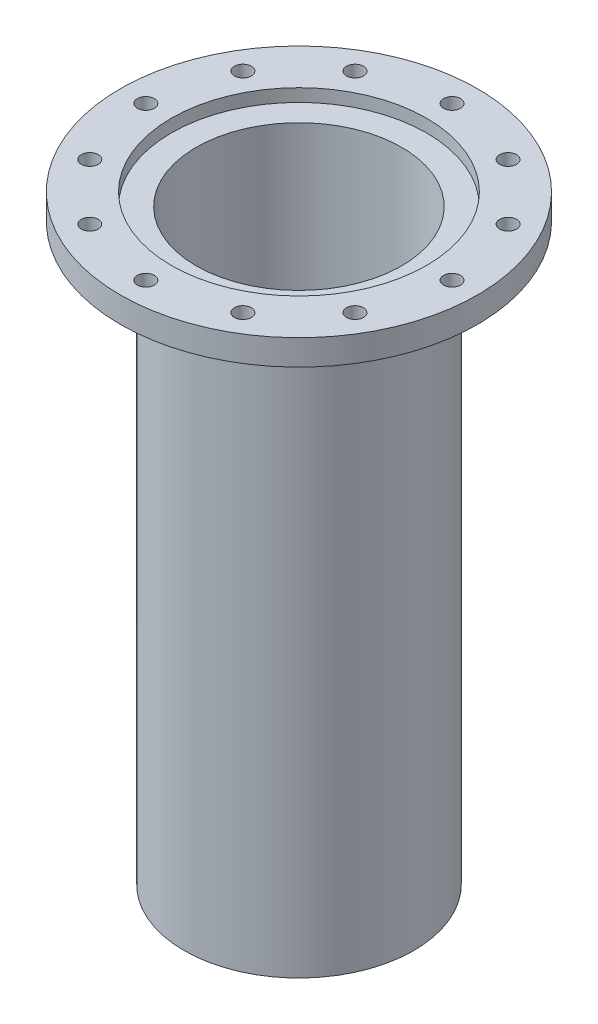
SolidWorks part; units mm, degrees
ref_plane "Front Plane" through (0, 0, 0) normal (0, 0, 1) x (1, 0, 0)
ref_plane "Top Plane" through (0, 0, 0) normal (0, 1, 0) x (1, 0, 0)
ref_plane "Right Plane" through (0, 0, 0) normal (1, 0, 0) x (0, 0, -1)
sketch "Sketch1" plane through (0, 0, 0) normal (0, 0, 1) x (1, 0, 0)
  line L0 (-63.5, 0) -> (-88.9, 0)
  line L1 (-88.9, 0) -> (-88.9, -12.7)
  line L2 (-88.9, -12.7) -> (-57.15, -12.7)
  line L3 (-57.15, -12.7) -> (-57.15, -298.45)
  line L4 (-57.15, -298.45) -> (-51.1302, -298.45)
  line L5 (-51.1302, -298.45) -> (-51.1302, -6.35)
  line L6 (-51.1302, -6.35) -> (-63.5, -6.35)
  line L7 (-63.5, -6.35) -> (-63.5, 0)
  line L8 (0, 0) -> (0, -50.8318) construction
  dimension "D1" = 51.1302
  dimension "D2" = 292.1
  dimension "D3" = 57.15
  dimension "D4" = 12.7
  dimension "D5" = 88.9
  dimension "D6" = 6.35
  dimension "D7" = 63.5
revolve "Revolve1" add sketch "Sketch1" angle 360 about L8
hole_wizard "5/16 Clearance Hole1" positions "Sketch2" profile "Sketch3" hole size "5/16" standard "ANSI Inch" end condition through all
sketch "Sketch2" plane through (0, 0, 0) normal (0, 1, 0) x (1, 0, 0)
  point P0 (-76.2, 0)
  dimension "D1" = 76.2
sketch "Sketch3" plane through (-76.2, 0, 0) normal (1, 0, 0) x (0, 0, 1)
  line L0 (0, 0) -> (0, 298.45)
  line L1 (0, 298.45) -> (4.2164, 298.45)
  line L2 (4.2164, 298.45) -> (4.2164, 0)
  line L5 (4.2164, 0) -> (0, 0)
  line L11 (0, -6.35) -> (0, 107.95) construction
  dimension "Thru Hole Dia." = 8.4328
  dimension "Thru Hole Depth" = 298.45
pattern_circular "CirPattern1" count 12 over 360 about axis through (0, 0, 0) along (0, 1, 0) of "5/16 Clearance Hole1" reverse direction yes
